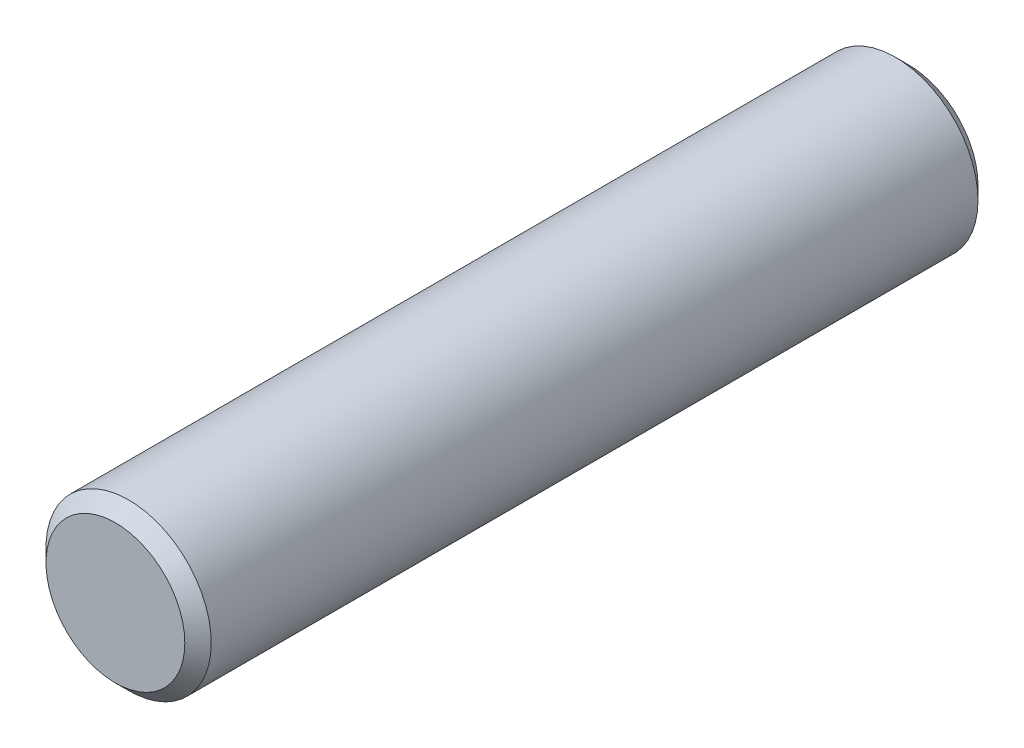
SolidWorks part; units mm, degrees
ref_plane "Ebene vorne" through (0, 0, 0) normal (0, 0, 1) x (1, 0, 0)
ref_plane "Ebene oben" through (0, 0, 0) normal (0, 1, 0) x (1, 0, 0)
ref_plane "Ebene rechts" through (0, 0, 0) normal (1, 0, 0) x (0, 0, -1)
sketch "Skizze1" plane through (0, 0, 0) normal (0, 0, 1) x (1, 0, 0)
  circle A0 centre (0, 0) radius 1.25
  dimension "D1" = 2.5
extrude "Aufsatz-Linear austragen1" add sketch "Skizze1" along normal blind 6 and the other way blind 6
ref_axis "Achse1" through (0, 0, -15.4) along (0, 0, 1)
chamfer "Fase1" distance 0.2 angle 45 2 edges at (1.25, 0, -6) (1.25, 0, 6)
